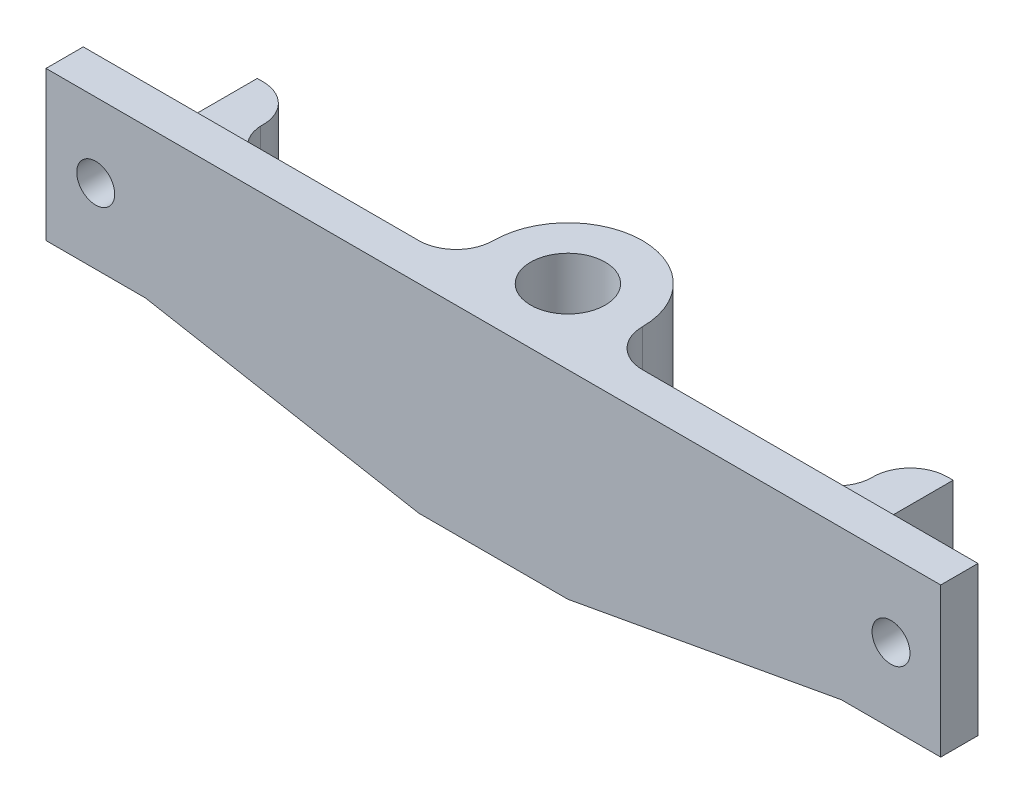
SolidWorks part; units mm, degrees
ref_plane "Front Plane" through (0, 0, 0) normal (0, 0, 1) x (1, 0, 0)
ref_plane "Top Plane" through (0, 0, 0) normal (0, 1, 0) x (1, 0, 0)
ref_plane "Right Plane" through (0, 0, 0) normal (1, 0, 0) x (0, 0, -1)
sketch "Sketch3" plane through (0, 0, 0) normal (0, 0, 1) x (1, 0, 0)
  line L0 (-57.15, 0) -> (57.15, 0)
  line L1 (57.15, 0) -> (57.15, -19.05)
  line L2 (57.15, -19.05) -> (44.45, -19.05)
  line L3 (0, 0) -> (0, -35.6763) construction
  line L4 (-57.15, -19.05) -> (-44.45, -19.05)
  line L5 (-57.15, 0) -> (-57.15, -19.05)
  line L6 (-9.525, -25.4) -> (9.525, -25.4)
  line L7 (-44.45, -19.05) -> (-9.525, -25.4)
  line L8 (9.525, -25.4) -> (44.45, -19.05)
  point P12 (0, -25.4)
  dimension "D1" = 114.3
  dimension "D2" = 19.05
  dimension "D3" = 12.7
  dimension "D4" = 25.4
extrude "Boss-Extrude5" add sketch "Sketch3" along normal blind 4.7625
hole_wizard "#11 (0.191) Diameter Hole1" positions "3DSketch1" profile "Sketch5" hole size "#11" standard "ANSI Inch" end condition up to next
sketch3d "3DSketch1"
  line L0 (57.15, -19.05, 4.7625) -> (57.15, 0, 4.7625) construction
  line L1 (57.15, 0, 4.7625) -> (-57.15, 0, 4.7625) construction
  point P0 (50.8, -9.525, 4.7625)
  point P7 (-50.8, -9.525, 4.7625)
  dimension "D1" = 6.35
  dimension "D2" = 9.525
sketch "Sketch5" plane through (50.8, -9.525, 4.7625) normal (1, 0, 0) x (0, -1, 0)
  line L0 (0, 0) -> (0, 4.7625)
  line L1 (0, 4.7625) -> (2.4257, 4.7625)
  line L2 (2.4257, 4.7625) -> (2.4257, 0)
  line L5 (2.4257, 0) -> (0, 0)
  line L11 (0, -6.35) -> (0, 107.95) construction
  dimension "Thru Hole Dia." = 4.8514
  dimension "Thru Hole Depth" = 4.7625
sketch "Sketch6" plane through (0, -25.4, 0) normal (0, -1, 0) x (1, 0, 0)
  line L0 (9.525, 0) -> (9.525, -4.7625)
  line L1 (-9.525, 0) -> (9.525, 0) construction
  line L2 (0, -55) -> (0, 55) construction
  line L3 (-9.525, 0) -> (-9.525, -4.7625)
  line L4 (-9.525, 0) -> (9.525, 0)
  arc A0 (-9.525, -4.7625) -> (9.525, -4.7625) centre (0, -4.7625) ccw
  dimension "D1" = 9.525
extrude "Boss-Extrude6" add sketch "Sketch6" against normal blind 25.4
sketch "Sketch7" plane through (0, -25.4, 0) normal (0, -1, 0) x (1, 0, 0)
  circle A0 centre (0, -4.7625) radius 4.7625
extrude "Cut-Extrude1" cut sketch "Sketch7" against normal through all both and the other way through all
fillet "Fillet2" radius 4.7625 2 edges at (-9.525, -12.7, 0) (9.525, -12.7, 0)
ref_plane "Plane1" through (0, -9.525, 0) normal (0, -1, 0) x (-1, 0, 0)
sketch "Sketch8" plane through (0, -9.525, 0) normal (0, -1, 0) x (-1, 0, 0)
  line L0 (-44.45, 0) -> (-44.45, 9.525)
  line L1 (-44.45, 9.525) -> (-43.7237, 9.525)
  line L8 (-44.45, 0) -> (-34.2184, 0)
  arc A0 (-43.7237, 9.525) -> (-38.971, 4.4568) centre (-43.7237, 4.7625) cw
  arc A1 (-34.2184, 0) -> (-38.971, 4.4568) centre (-34.2184, 4.7625) cw
  dimension "D1" = 4.7625
  dimension "D2" = 4.7625
  dimension "D3" = 9.525
extrude "Boss-Extrude7" add sketch "Sketch8" along normal mid plane 15.24
mirror "Mirror1" about plane through (0, 0, 0) normal (1, 0, 0) of "Boss-Extrude7"
